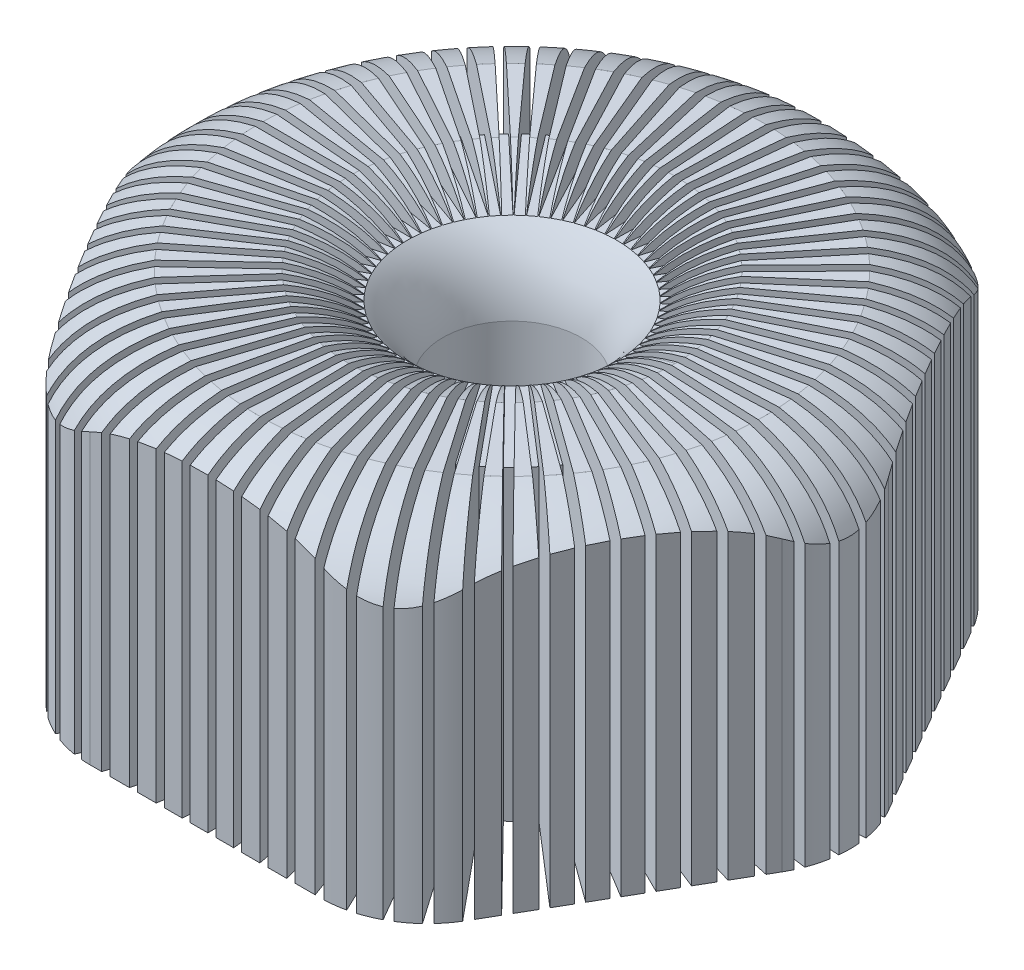
SolidWorks part; units mm, degrees
ref_plane "Front Plane" through (0, 0, 0) normal (0, 0, 1) x (1, 0, 0)
ref_plane "Top Plane" through (0, 0, 0) normal (0, 1, 0) x (1, 0, 0)
ref_plane "Right Plane" through (0, 0, 0) normal (1, 0, 0) x (0, 0, -1)
sketch "Sketch1" plane through (0, 0, 0) normal (0, 1, 0) x (1, 0, 0)
  line L1 (60.6218, 10) -> (38.9711, 47.5)
  line L2 (21.6506, 57.5) -> (-21.6506, 57.5)
  line L3 (-38.9711, 47.5) -> (-60.6218, 10)
  line L4 (-60.6218, -10) -> (-38.9711, -47.5)
  line L5 (-21.6506, -57.5) -> (21.6506, -57.5)
  line L6 (38.9711, -47.5) -> (60.6218, -10)
  circle A0 centre (0, 0) radius 57.5 construction
  arc A1 (-21.6506, -57.5) -> (-38.9711, -47.5) centre (-21.6506, -37.5) cw
  arc A2 (21.6506, -57.5) -> (38.9711, -47.5) centre (21.6506, -37.5) ccw
  arc A3 (60.6218, -10) -> (60.6218, 10) centre (43.3013, 0) ccw
  arc A4 (38.9711, 47.5) -> (21.6506, 57.5) centre (21.6506, 37.5) ccw
  arc A5 (-21.6506, 57.5) -> (-38.9711, 47.5) centre (-21.6506, 37.5) ccw
  arc A6 (-60.6218, -10) -> (-60.6218, 10) centre (-43.3013, 0) cw
  dimension "D1" = 115
  dimension "D2" = 20
extrude "Boss-Extrude2" add sketch "Sketch1" along normal blind 62.5
sketch "Sketch6" plane through (0, 62.5, 0) normal (0, 1, 0) x (1, 0, 0)
  circle A0 centre (0, 0) radius 13
extrude "Cut-Extrude1" cut sketch "Sketch6" against normal up to surface (62.5 mm away) up to face at (0, 0, 0)
sketch "Sketch7" plane through (0, 0, 0) normal (0, 0, 1) x (1, 0, 0)
  line L0 (0, 62.5) -> (0, 0) construction
  line L1 (-21.6506, 62.5) -> (21.6506, 62.5) construction
  line L2 (0, 62.5) -> (13, 62.5) construction
  line L3 (13, 62.5) -> (13, 45)
  line L4 (13, 62.5) -> (30.5, 62.5)
  line L5 (38.9711, 62.5) -> (21.6506, 62.5) construction
  line L6 (13, 0) -> (63.3013, 0) construction
  line L7 (38.9711, 0) -> (38.9711, 62.5) construction
  line L8 (64.9423, 62.5) -> (47.4423, 62.5)
  line L9 (64.9423, 62.5) -> (64.9423, 45)
  line L10 (13, 62.5) -> (-13, 62.5) construction
  line L11 (13, 62.5) -> (18.1614, 56.1261) construction
  spline S0 degree 2 poles (13, 45) (15.1116, 59.0525) (30.5, 62.5) knots 0 0 0 1 1 1
  spline S1 degree 2 poles (64.9423, 45) (62.8306, 59.0525) (47.4423, 62.5) knots 0 0 0 1 1 1
  point P23 (14.4311, 51.6302)
  dimension "D1" = 13
  dimension "D2" = 17.5
  dimension "D3" = 17.5
  dimension "D4" = 8.2017
revolve "Cut-Revolve1" cut sketch "Sketch7" angle 360 about L0
ref_plane "Plane1" through (0, 31.25, 0) normal (0, 1, 0) x (1, 0, 0)
sketch "Sketch8" plane through (0, 0, 0) normal (0, 0, 1) x (1, 0, 0)
  line L0 (-63.3013, 62.5) -> (-63.3013, 0)
  line L1 (-13.3013, 5) -> (-38.3013, 5) construction
  line L2 (-38.3013, 5) -> (-38.3013, 0)
  line L3 (-63.3013, 0) -> (-38.3013, 0)
  line L4 (-13.3013, 0) -> (-13.3013, 5) construction
  line L5 (-38.3013, 5) -> (-38.3013, 57.5)
  line L6 (63.25, 31.25) -> (-63.25, 31.25) construction
  line L7 (-63.3013, 31.25) -> (-38.3013, 31.25) construction
  line L8 (-13.3013, 62.5) -> (-13.3013, 57.5)
  line L9 (-63.3013, 62.5) -> (-13.3013, 62.5)
  line L10 (-13.3013, 57.5) -> (-38.3013, 57.5)
  line L11 (-38.3013, 0) -> (-13.3013, 0) construction
  point P3 (-66.188, 24)
  dimension "D1" = 50
  dimension "D2" = 50
  dimension "D3" = 5
  dimension "D4" = 25
extrude "Cut-Extrude2" cut sketch "Sketch8" against normal blind 0.75 and the other way blind 0.75
pattern_circular "CirPattern1" count 75 over 360 about axis through (0, -36.7696, 0) along (0, 1, 0) of "Cut-Extrude2"
